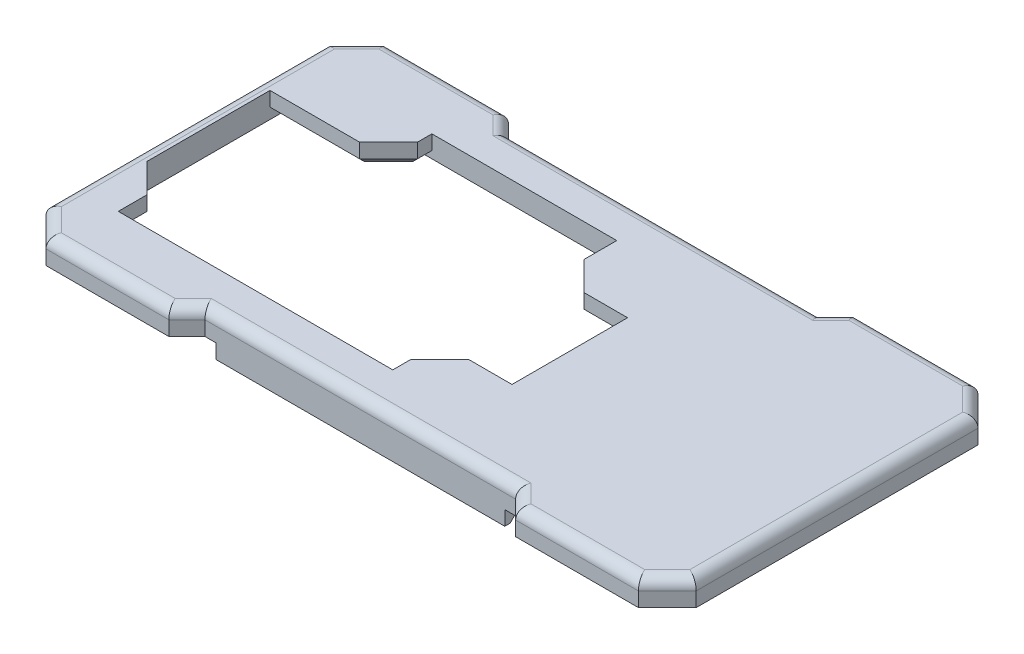
SolidWorks part; units mm, degrees
ref_plane "Front Plane" through (0, 0, 0) normal (0, 0, 1) x (1, 0, 0)
ref_plane "Top Plane" through (0, 0, 0) normal (0, 1, 0) x (1, 0, 0)
ref_plane "Right Plane" through (0, 0, 0) normal (1, 0, 0) x (0, 0, -1)
sketch "Sketch1" plane through (0, 0, 0) normal (0, 1, 0) x (1, 0, 0)
  line L1 (0, 0) -> (90, 0)
  line L2 (0, 0) -> (0, 47)
  line L3 (0, 47) -> (90, 47)
  line L4 (90, 0) -> (90, 47)
extrude "Boss-Extrude1" add sketch "Sketch1" along normal blind 3.5
sketch "Sketch2" plane through (0, 3.5, 0) normal (0, 1, 0) x (1, 0, 0)
  line L0 (0, 23.5) -> (2, 23.5) construction
  line L1 (0, 47) -> (0, 0) construction
  line L2 (2, 23.5) -> (2, 40.5)
  line L3 (2, 23.5) -> (2, 6.5)
  line L4 (2, 6.5) -> (54, 6.5)
  line L5 (2, 40.5) -> (54, 40.5)
  line L6 (54, 40.5) -> (54, 6.5)
  line L8 (0, 0) -> (90, 0) construction
  dimension "D1" = 2
  dimension "D2" = 34
  dimension "D3" = 6.5
  dimension "D4" = 52
extrude "Cut-Extrude1" cut sketch "Sketch2" along normal through all from surface starting at face at (45, 0, -23.5)
fillet "Fillet1" radius 6.4 2 edges at (2, 1.75, -6.5) (54, 1.75, -40.5)
sketch "Sketch4" plane through (0, 3.5, 0) normal (0, 1, 0) x (1, 0, 0)
  line L0 (0, 23.5) -> (13, 23.5) construction
  line L1 (0, 47) -> (0, 0) construction
  line L2 (13, 23.5) -> (13, 43.75) construction
  line L3 (45, 47) -> (45, 0) construction
  line L4 (90, 47) -> (0, 47) construction
  line L5 (0, 0) -> (90, 0) construction
  circle A0 centre (13, 43.75) radius 2.55
  circle A1 centre (13, 3.25) radius 2.55
  circle A2 centre (77, 3.25) radius 2.55
  circle A3 centre (77, 43.75) radius 2.55
  dimension "D1" = 13
  dimension "D2" = 20.25
extrude "Cut-Extrude3" cut sketch "Sketch4" along normal blind 3.2 from surface starting at face at (28, 0, -23.5)
sketch "Sketch5" plane through (0, 3.5, 0) normal (0, 1, 0) x (1, 0, 0)
  line L0 (45, 0) -> (45, 4)
  line L1 (0, 0) -> (90, 0) construction
  line L2 (45, 4) -> (65, 4)
  line L3 (65, 4) -> (65, 0)
  line L4 (65, 0) -> (45, 0)
  line L5 (45, 4) -> (25, 4)
  line L6 (25, 4) -> (25, 0)
  line L7 (25, 0) -> (45, 0)
  line L8 (0, 23.5) -> (90, 23.5) construction
  line L9 (0, 47) -> (0, 0) construction
  line L10 (90, 0) -> (90, 47) construction
  line L11 (25, 47) -> (45, 47)
  line L12 (25, 43) -> (25, 47)
  line L13 (45, 43) -> (25, 43)
  line L14 (65, 47) -> (45, 47)
  line L15 (65, 43) -> (65, 47)
  line L16 (45, 43) -> (65, 43)
  line L17 (45, 47) -> (45, 43)
  line M15 (0, 0) -> (90, 0)
  line M19 (90, 47) -> (0, 47)
  dimension "D1" = 4
  dimension "D2" = 20
  dimension "D3" = 20
extrude "Cut-Extrude4" cut sketch "Sketch5" against normal blind 21.1 contours L5 L6 L0 M15 | L3 L2 L0 M15 | L17 L12 L13 M19 | L17 L16 L15 M19 region at (35, 3.5, -2) region at (55, 3.5, -2) region at (35, 3.5, -45) region at (55, 3.5, -45)
chamfer "Chamfer1" distance 4 angle 45 8 edges at (90, 1.75, 0) (90, 1.75, -47) (0, 1.75, -47) (0, 1.75, 0) (25, 1.75, -47) (65, 1.75, -47) (65, 1.75, 0) (25, 1.75, 0)
sketch "Sketch6" plane through (0, 3.5, 0) normal (0, 1, 0) x (1, 0, 0)
  line L0 (54, 6.5) -> (54, 14.5)
  line L1 (54, 34.1) -> (54, 6.5) construction
  line L2 (54, 14.5) -> (44, 14.5)
  line L3 (44, 14.5) -> (44, 8)
  line L4 (54, 6.5) -> (8.4, 6.5) construction
  line L5 (42, 6.5) -> (54, 6.5)
  line L6 (44, 8) -> (6, 8)
  line L7 (6, 8) -> (6, 16)
  line L8 (6, 16) -> (2, 16)
  line L9 (2, 12.9) -> (2, 40.5) construction
  line L10 (2, 16) -> (2, 6.5)
  line L11 (2, 6.5) -> (42, 6.5)
  line L12 (47.6, 40.5) -> (54, 40.5)
  line L13 (54, 40.5) -> (54, 30.5)
  line L14 (54, 30.5) -> (44, 30.5)
  line L15 (44, 30.5) -> (44, 39)
  line L17 (2, 40.5) -> (2, 33)
  line L18 (2, 33) -> (18.4128, 33)
  line L19 (44, 39) -> (18.4128, 39)
  line L20 (18.4128, 39) -> (18.4128, 33)
  line L21 (2, 40.5) -> (47.6, 40.5)
  dimension "D1" = 8
  dimension "D2" = 10
  dimension "D3" = 6.5
  dimension "D4" = 10
  dimension "D5" = 4
  dimension "D6" = 9.5
  dimension "D7" = 7.5
extrude "Boss-Extrude2" add sketch "Sketch6" against normal blind 3
chamfer "Chamfer2" distance 4 angle 45 3 edges at (18.4128, 2, -33) (44, 2, -14.5) (44, 2, -30.5)
chamfer "Chamfer3" distance 4 angle 45 1 edges at (6, 2, -16)
sketch "Sketch7" plane through (0, 0, 0) normal (0, -1, 0) x (1, 0, 0)
  line L0 (65, -22.5) -> (56, -22.5)
  line L3 (56, -40.5) -> (74, -40.5)
  line L4 (74, -40.5) -> (74, -22.5)
  line L5 (56, -6.5) -> (74, -6.5)
  line L6 (57.5, -6.5) -> (72.5, -6.5) construction
  line L7 (56, -40.5) -> (56, -22.5)
  line L8 (57.5, -22.5) -> (72.5, -22.5) construction
  line L9 (65, -22.5) -> (74, -22.5)
  line L10 (65, -21.5) -> (74, -21.5)
  line L11 (72.5, -21.5) -> (57.5, -21.5) construction
  line L12 (65, -21.5) -> (56, -21.5)
  line L16 (88, -40.5) -> (88, -6.5)
  line L17 (88, -6.5) -> (76, -6.5)
  line L18 (76, -6.5) -> (76, -40.5)
  line L19 (88, -40.5) -> (76, -40.5)
  line L20 (74, -21.5) -> (74, -6.5)
  line L21 (56, -21.5) -> (56, -6.5)
  point P9 (65, -6.5)
extrude "Cut-Extrude5" cut sketch "Sketch7" against normal blind 2.5
fillet "Fillet2" radius 1.5 12 edges at (56, 1.25, -40.5) (74, 1.25, -22.5) (74, 1.25, -21.5) (74, 1.25, -40.5) (76, 1.25, -40.5) (88, 1.25, -40.5) (74, 1.25, -6.5) (76, 1.25, -6.5) (88, 1.25, -6.5) (56, 1.25, -6.5) (56, 1.25, -22.5) (56, 1.25, -21.5)
chamfer "Chamfer4" distance 1 angle 45 11 edges at (51, 0.5, -14.5) (46, 0.5, -12.5) (44, 0.5, -9.25) (6, 0.5, -10) (4, 0.5, -14) (8.2064, 0.5, -33) (16.4128, 0.5, -35) (18.4128, 0.5, -38) (44, 0.5, -36.75) (51, 0.5, -30.5) (46, 0.5, -32.5)
sketch "Sketch8" plane through (0, 3.5, 0) normal (0, 1, 0) x (1, 0, 0)
  line L0 (45, 4) -> (45, 2.5)
  line L1 (65, 4) -> (25, 4) construction
  line L2 (45, 2.5) -> (66.5, 2.5)
  line L3 (65, 4) -> (69, 0) construction
  line L4 (66.5, 2.5) -> (65, 4)
  line L5 (65, 4) -> (25, 4)
  line L6 (25, 4) -> (23.5, 2.5)
  line L7 (21, 0) -> (25, 4) construction
  line L8 (23.5, 2.5) -> (45, 2.5)
  line L9 (90, 23.5) -> (74.5605, 23.5) construction
  line L11 (23.5, 44.5) -> (45, 44.5)
  line L12 (25, 43) -> (23.5, 44.5)
  line L13 (65, 43) -> (25, 43)
  line L14 (66.5, 44.5) -> (65, 43)
  line L15 (45, 44.5) -> (66.5, 44.5)
  line L16 (45, 43) -> (45, 44.5)
  line M22 (65, 43) -> (25, 43)
  line M23 (25, 43) -> (21, 47)
  line M29 (21, 0) -> (25, 4)
  line M30 (25, 4) -> (65, 4)
  line M31 (65, 4) -> (69, 0)
  line M37 (69, 47) -> (65, 43)
extrude "Boss-Extrude3" add sketch "Sketch8" against normal blind 5.5 contours L0 L2 M31 M30 | L8 L0 M29 M30 | L16 L15 M22 M37 | L13 L16 L11 M23 region at (55.3795, 3.5, -3.241) region at (34.6205, 3.5, -3.241) region at (34.6205, 3.5, -43.759) region at (55.3795, 3.5, -43.759)
sketch "Sketch10" plane through (0, -2, 0) normal (0, -1, 0) x (-1, 0, 0)
  line L0 (-25, 4) -> (-25, 2.5)
  line L1 (-23.5, 2.5) -> (-66.5, 2.5) construction
  line L2 (-25, 2.5) -> (-23.5, 2.5)
  line L3 (-23.5, 2.5) -> (-25, 4)
  line L4 (-65, 4) -> (-65, 2.5)
  line L5 (-65, 2.5) -> (-66.5, 2.5)
  line L6 (-66.5, 2.5) -> (-65, 4)
  line L7 (-65, 43) -> (-65, 44.5)
  line L8 (-23.5, 44.5) -> (-66.5, 44.5) construction
  line L9 (-65, 44.5) -> (-66.5, 44.5)
  line L10 (-66.5, 44.5) -> (-65, 43)
  line L11 (-25, 43) -> (-25, 44.5)
  line L12 (-25, 44.5) -> (-23.5, 44.5)
  line L13 (-23.5, 44.5) -> (-25, 43)
extrude "Cut-Extrude6" cut sketch "Sketch10" against normal up to surface (2 mm away) up to face at (82, 0, -23.5)
chamfer "Chamfer6" distance 0.75 angle 45 2 edges at (45, -2, -43) (45, -2, -4)
fillet "Fillet3" radius 1.5 16 edges at (77.5, 3.5, 0) (88, 3.5, -2) (67.75, 3.5, -1.25) (67.75, 3.5, -45.75) (77.5, 3.5, -47) (88, 3.5, -45) (90, 3.5, -23.5) (22.25, 3.5, -45.75) (45, 3.5, -44.5) (2, 3.5, -45) (12.5, 3.5, -47) (0, 3.5, -23.5) (2, 3.5, -2) (12.5, 3.5, 0) (22.25, 3.5, -1.25) (45, 3.5, -2.5)
